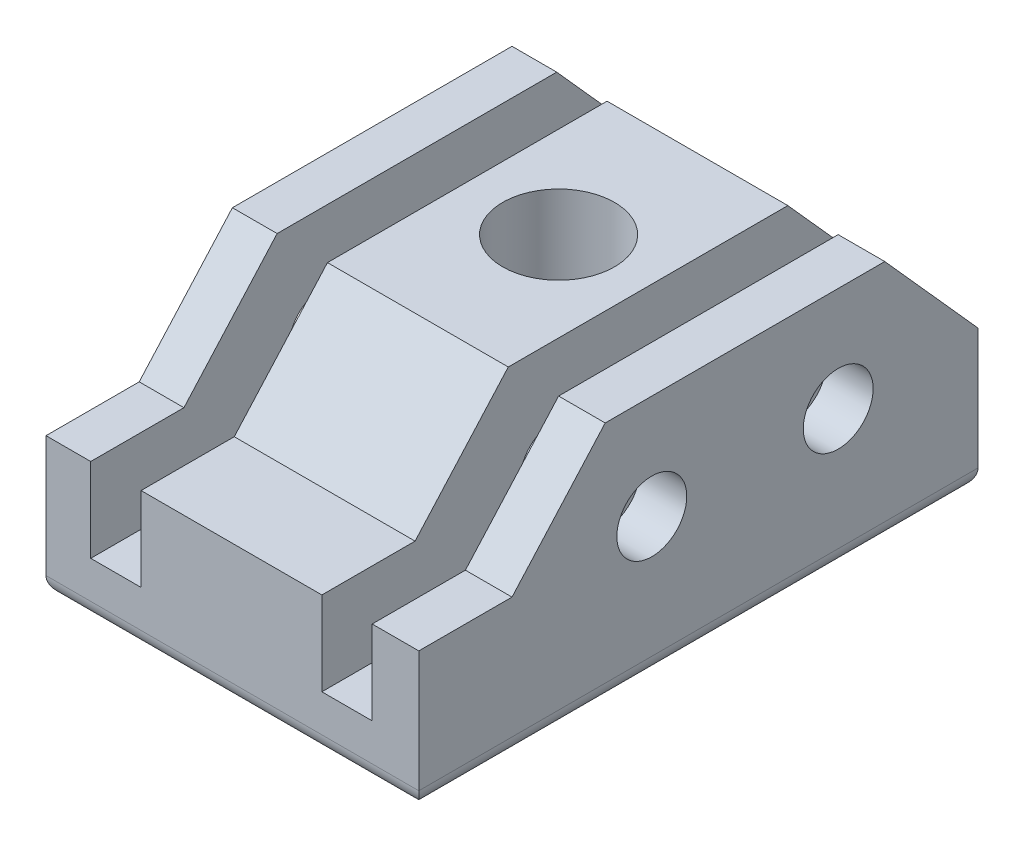
SolidWorks part; units mm, degrees
ref_plane "Front Plane" through (0, 0, 0) normal (0, 0, 1) x (1, 0, 0)
ref_plane "Top Plane" through (0, 0, 0) normal (0, 1, 0) x (1, 0, 0)
ref_plane "Right Plane" through (0, 0, 0) normal (1, 0, 0) x (0, 0, -1)
sketch "Sketch1" plane through (0, 0, 0) normal (1, 0, 0) x (0, 0, -1)
  line L1 (0, 0) -> (63.5, 0)
  line L2 (0, 0) -> (0, 6.35)
  line L3 (0, 6.35) -> (63.5, 6.35)
  line L4 (63.5, 0) -> (63.5, 6.35)
  dimension "D1" = 6.35
  dimension "D2" = 63.5
extrude "Boss-Extrude1" add sketch "Sketch1" against normal blind 50.8
sketch "Sketch2" plane through (0, 0, 0) normal (1, 0, 0) x (0, 0, -1)
  line L0 (0, 6.35) -> (0, 19.05)
  line L1 (0, 19.05) -> (12.7, 33.249)
  line L2 (12.7, 33.249) -> (50.8, 33.249)
  line L3 (50.8, 33.249) -> (63.5, 19.05)
  line L4 (63.5, 19.05) -> (63.5, 6.35)
  line L5 (63.5, 6.35) -> (0, 6.35)
  point P7 (31.75, 33.249)
  point P10 (31.75, 6.35)
  dimension "D1" = 38.1
  dimension "D2" = 12.7
  dimension "D3" = 12.7
  dimension "D4" = 19.05
  dimension "D5" = 19.05
extrude "Boss-Extrude2" add sketch "Sketch2" against normal blind 50.8
sketch "Sketch10" plane through (0, 0, -63.5) normal (0, 0, -1) x (-1, 0, 0)
  line L1 (50.8, 33.249) -> (0, 33.249) construction
  line L3 (6.35, 7.62) -> (6.35, 33.249)
  line L4 (6.35, 33.249) -> (13.208, 33.249)
  line L5 (13.208, 7.62) -> (13.208, 33.249)
  line L6 (6.35, 7.62) -> (13.208, 7.62)
  line L8 (50.8, 0) -> (0, 0) construction
  point P11 (13.208, 7.62)
  dimension "D1" = 7.62
  dimension "D2" = 6.858
  dimension "D3" = 6.35
extrude "Cut-Extrude1" cut sketch "Sketch10" against normal through all
pattern_linear "LPattern3" count 2 spacing 31.496 along (-1, 0, 0) of "Cut-Extrude1"
sketch "Sketch11" plane through (0, 0, 0) normal (1, 0, 0) x (0, 0, -1)
  circle A0 centre (19.05, 19.05) radius 4.7625
  circle A1 centre (19.05, 19.05) radius 7.9375 construction
  circle A2 centre (44.45, 19.05) radius 4.7625
  circle A3 centre (44.45, 19.05) radius 7.9375 construction
  dimension "D1" = 9.525
  dimension "D3" = 15.875
  dimension "D4" = 9.525
  dimension "D6" = 15.875
  dimension "D2" = 6.35
  dimension "D5" = 6.35
extrude "Cut-Extrude2" cut sketch "Sketch11" against normal through all
sketch "Sketch14" plane through (0, 33.249, 0) normal (0, 1, 0) x (1, 0, 0)
  line L3 (-37.846, 12.7) -> (-37.846, 50.8) construction
  point P0 (-25.4, 31.75)
  point P4 (-37.846, 31.75)
  dimension "D1" = 12.446
sketch "Sketch17" plane through (0, 40.0201, -44.7438) normal (0, 0.6667, -0.7454) x (-1, 0, 0)
  line L0 (13.208, -28.1343) -> (13.208, -9.0843) construction
  line L1 (37.846, -9.0843) -> (13.208, -9.0843) construction
  point P0 (25.527, -18.6093)
  point P4 (13.208, -18.6093)
  point P7 (25.527, -9.0843)
sketch "Sketch18" plane through (0, 8.4667, 9.466) normal (0, 0.6667, 0.7454) x (1, 0, 0)
  line L0 (-13.208, 33.249) -> (-13.208, 14.199) construction
  line L1 (-37.846, 33.249) -> (-13.208, 33.249) construction
  point P0 (-25.527, 23.724)
  point P1 (-25.527, 23.724)
  point P4 (-13.208, 23.724)
  point P7 (-25.527, 33.249)
ref_plane "Plane2" through (0, 33.02, 0) normal (0, -1, 0) x (-1, 0, 0)
fillet "Fillet1" [suppressed] radius 2.54
sketch "Sketch22" plane through (0, 0, 0) normal (0, 0, 1) x (1, 0, 0)
  line L0 (-50.8, 19.05) -> (-50.8, 0) construction
  line L1 (0, 0) -> (-50.8, 0)
  line L2 (0, 0) -> (0, 7.62)
  line L3 (-6.35, 7.62) -> (-13.208, 7.62)
  line L4 (-50.8, 0) -> (-50.8, 7.62)
  line L5 (-37.846, 7.62) -> (-37.846, 19.05)
  line L6 (-37.846, 19.05) -> (-13.208, 19.05)
  line L7 (-13.208, 19.05) -> (-13.208, 7.62)
  line L8 (-37.846, 7.62) -> (-44.704, 7.62)
  line L9 (-50.8, 7.62) -> (-50.8, 19.05)
  line L10 (-50.8, 19.05) -> (-44.704, 19.05)
  line L11 (-44.704, 19.05) -> (-44.704, 7.62)
  line L12 (-6.35, 7.62) -> (-6.35, 19.05)
  line L13 (-6.35, 19.05) -> (0, 19.05)
  line L14 (0, 19.05) -> (0, 7.62)
extrude "Boss-Extrude3" add sketch "Sketch22" along normal blind 12.7
sketch "Sketch23" plane through (0, 33.249, 0) normal (0, 1, 0) x (1, 0, 0)
  line L0 (-25.4, 63.5) -> (-25.4, -12.7) construction
  line L1 (-50.8, 63.5) -> (0, 63.5) construction
  line L2 (-50.8, -12.7) -> (0, -12.7) construction
  circle A0 centre (-25.4, 31.75) radius 7.62
  point P15 (-34.579, 50.8)
  dimension "D1" = 15.24
extrude "Cut-Extrude6" cut sketch "Sketch23" against normal through all
fillet "Fillet2" radius 2.54 4 edges at (-25.4, 0, -63.5) (-50.8, 0, -25.4) (-25.4, 0, 12.7) (0, 0, -25.4)
sketch "Sketch24" plane through (0, 0, 0) normal (0, -1, 0) x (1, 0, 0)
  line L0 (-20.4, -46.15) -> (-30.4, -46.15) construction
  line L1 (-25.4, -60.96) -> (-25.4, 10.16) construction
  line L2 (-48.26, -60.96) -> (-2.54, -60.96) construction
  line L3 (-2.54, 10.16) -> (-48.26, 10.16) construction
  line L4 (-20.4, 3.35) -> (-30.4, 3.35) construction
  circle A1 centre (-30.4, -46.15) radius 3.175
  circle A2 centre (-20.4, -46.15) radius 3.175
  circle A3 centre (-20.4, 3.35) radius 3.175
  circle A4 centre (-30.4, 3.35) radius 3.175
  circle A5 centre (-25.4, -31.75) radius 7.62 construction
  point P3 (-25.4, -46.15)
  point P12 (-25.4, 3.35)
  dimension "D2" = 6.35
  dimension "D1" = 10
  dimension "D3" = 49.5
  dimension "D4" = 14.4
extrude "Cut-Extrude7" cut sketch "Sketch24" against normal blind 10
